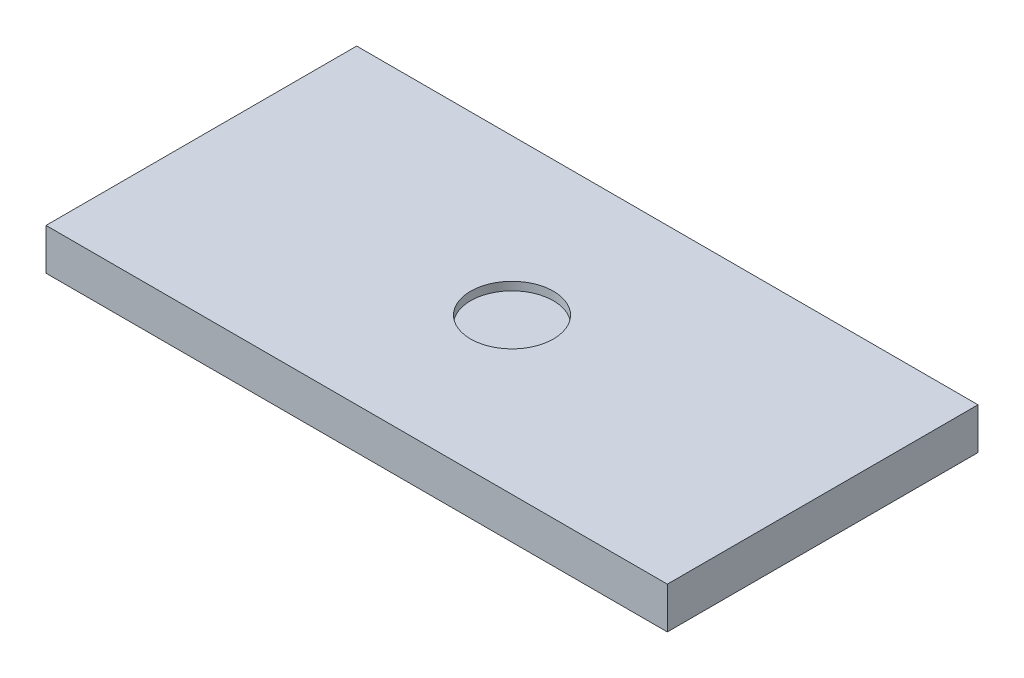
SolidWorks part; units mm, degrees
ref_plane "Front" through (0, 0, 0) normal (0, 0, 1) x (1, 0, 0)
ref_plane "Top" through (0, 0, 0) normal (0, 1, 0) x (1, 0, 0)
ref_plane "Right" through (0, 0, 0) normal (1, 0, 0) x (0, 0, -1)
sketch "草图1" plane through (0, 0, 0) normal (0, 1, 0) x (1, 0, 0)
  line L1 (-75, -37.5) -> (75, -37.5)
  line L2 (-75, -37.5) -> (-75, 37.5)
  line L3 (-75, 37.5) -> (75, 37.5)
  line L4 (75, -37.5) -> (75, 37.5)
  line L5 (-75, -37.5) -> (75, 37.5) construction
  line L6 (-75, 37.5) -> (75, -37.5) construction
  point P0 (0, 0)
  dimension "D1" = 150
  dimension "D2" = 75
extrude "凸台-拉伸1" add sketch "草图1" along normal blind 10
ref_axis "基准轴1" through (0, 50, 0) along (0, -1, 0)
sketch "草图2" plane through (0, 10, 0) normal (0, 1, 0) x (1, 0, 0)
  circle A0 centre (0, 0) radius 10
  dimension "D1" = 20
extrude "切除-拉伸1" cut sketch "草图2" against normal blind 2
